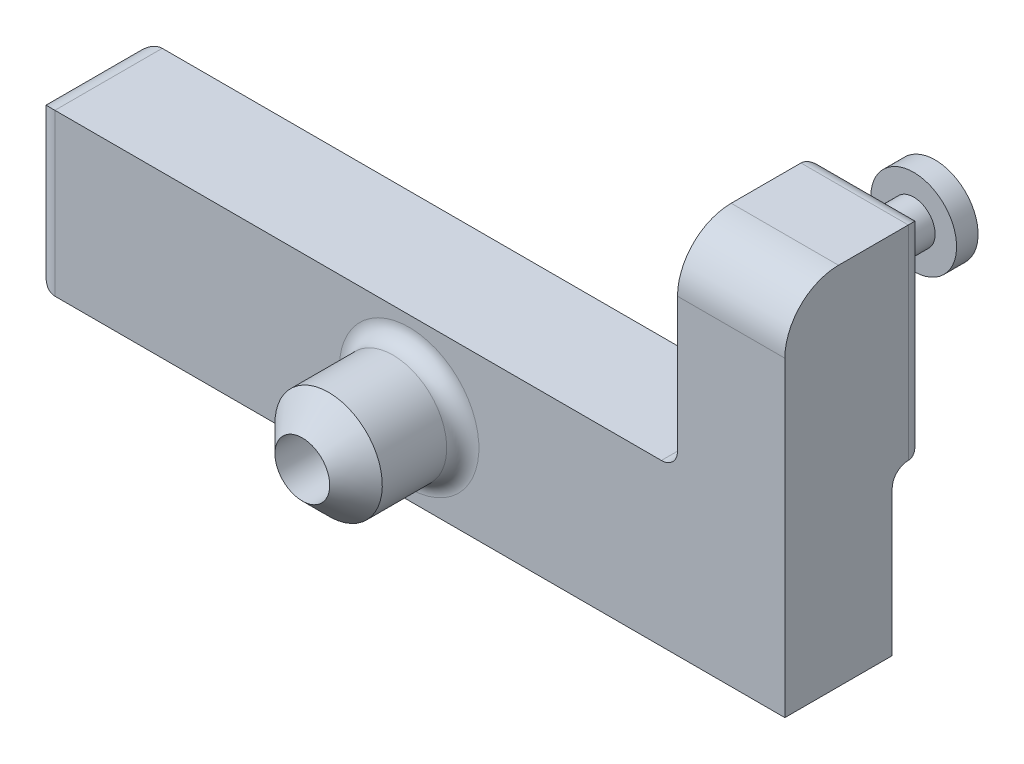
SolidWorks part; units mm, degrees
ref_plane "Front Plane" through (0, 0, 0) normal (0, 0, 1) x (1, 0, 0)
ref_plane "Top Plane" through (0, 0, 0) normal (0, 1, 0) x (1, 0, 0)
ref_plane "Right Plane" through (0, 0, 0) normal (1, 0, 0) x (0, 0, -1)
sketch "Sketch1" plane through (0, 0, 0) normal (0, 0, 1) x (1, 0, 0)
  line L0 (-35, -7.5) -> (35, -7.5)
  line L1 (-35, -7.5) -> (-35, 7.5)
  line L2 (35, -7.5) -> (35, 7.5)
  line L3 (-35, 7.5) -> (35, 7.5)
  line L4 (-35, -7.5) -> (35, 7.5) construction
  line L5 (35, -7.5) -> (-35, 7.5) construction
  circle A0 centre (0, 0) radius 2.55
  point P1 (0, 0)
  dimension "D3" = 5.1
  dimension "D1" = 70
  dimension "D2" = 15
  dimension "D4" = 35
extrude "Boss-Extrude1" add sketch "Sketch1" along normal blind 10
sketch "Sketch5" plane through (0, 0, 0) normal (0, 0, -1) x (-1, 0, 0)
  line L0 (-35, 26.5) -> (-25, 26.5)
  line L1 (-35, 26.5) -> (-35, 7.5)
  line L2 (-25, 26.5) -> (-25, 7.5)
  line L3 (-35, 7.5) -> (-25, 7.5)
  line L7 (-35, 7.5) -> (35, 7.5) construction
  line L8 (-35, -7.5) -> (-35, 7.5) construction
  dimension "D1" = 10
  dimension "D2" = 19
extrude "Boss-Extrude5" add sketch "Sketch5" against normal blind 10 and the other way blind 3 separate body
sketch "Sketch2" plane through (0, 0, 10) normal (0, 0, 1) x (1, 0, 0)
  line L0 (-35, 7.5) -> (-25, 7.5)
  line L1 (-35, 7.5) -> (-35, 17.5)
  line L2 (-25, 7.5) -> (-25, 17.5)
  line L3 (-35, 17.5) -> (-25, 17.5)
  line L4 (35, 7.5) -> (-35, 7.5) construction
  dimension "D1" = 10
  dimension "D2" = 10
extrude "Boss-Extrude2" [suppressed] add sketch "Sketch2" against normal blind 10
sketch "Sketch3" plane through (-35, 0, -3) normal (0, 0, -1) x (-1, 0, 0)
  line L0 (-70, -7.5) -> (-70, 7.5) construction
  line L1 (-60, 7.5) -> (-60, 26.5) construction
  line L2 (-60, 26.5) -> (-70, 26.5) construction
  circle A0 centre (-65, 21.5) radius 2
  point P9 (-60, 17)
  dimension "D1" = 4
  dimension "D2" = 5
  dimension "D3" = 5
fillet "Fillet1" radius 2 4 edges at (-35, 0, 0) (-35, -7.5, 5) (-35, 0, 10) (-35, 7.5, 5)
extrude "Boss-Extrude6" add sketch "Sketch3" along normal blind 4
sketch "Sketch6" plane through (0, 0, -7) normal (0, 0, -1) x (-1, 0, 0)
  circle A2 centre (-30, 21.5) radius 4
  circle A3 centre (-30, 21.5) radius 4
  dimension "D1" = 2
extrude "Boss-Extrude7" add sketch "Sketch6" along normal blind 2
fillet "Fillet4" radius 5 1 edges at (30, 26.5, 10)
combine bodies "Combine1" operation type add bodies to combine 106 105 107 101
fillet "Fillet7" [suppressed] radius 2
fillet "Fillet3" radius 1.5 5 edges at (30, 7.5, -3) (30, 7.5, 0) (25, 17, -3) (30, 26.5, -3) (35, 17, -3)
fillet "Fillet9" radius 1.5 2 edges at (25, 6.75, 0) (25, 7.5, 5)
sketch "Sketch8" plane through (0, 0, 0) normal (1, 0, 0) x (0, 0, -1)
  line L0 (-10, 0) -> (-20, 0)
  line L1 (-10, 21.5) -> (-10, -7.5) construction
  line L2 (-20, 0) -> (-20, 2.5)
  line L3 (-20, 2.5) -> (-17.5, 5)
  line L4 (-17.5, 5) -> (-10, 5)
  line L5 (-10, 5) -> (-10, 0)
  dimension "D1" = 2.5
  dimension "D2" = 5
  dimension "D3" = 10
  dimension "D4" = 135
revolve "Revolve1" add sketch "Sketch8" angle 360 about L0
sketch "Sketch9" plane through (0, 0, 10) normal (0, 0, -1) x (-1, 0, 0)
  circle A1 centre (0, 0) radius 2.55
  circle A2 centre (0, 0) radius 2.55
  dimension "D1" = 0
extrude "Cut-Extrude1" cut sketch "Sketch9" against normal blind 10
fillet "Fillet10" radius 1.5 1 edges at (0, 5, 10)
